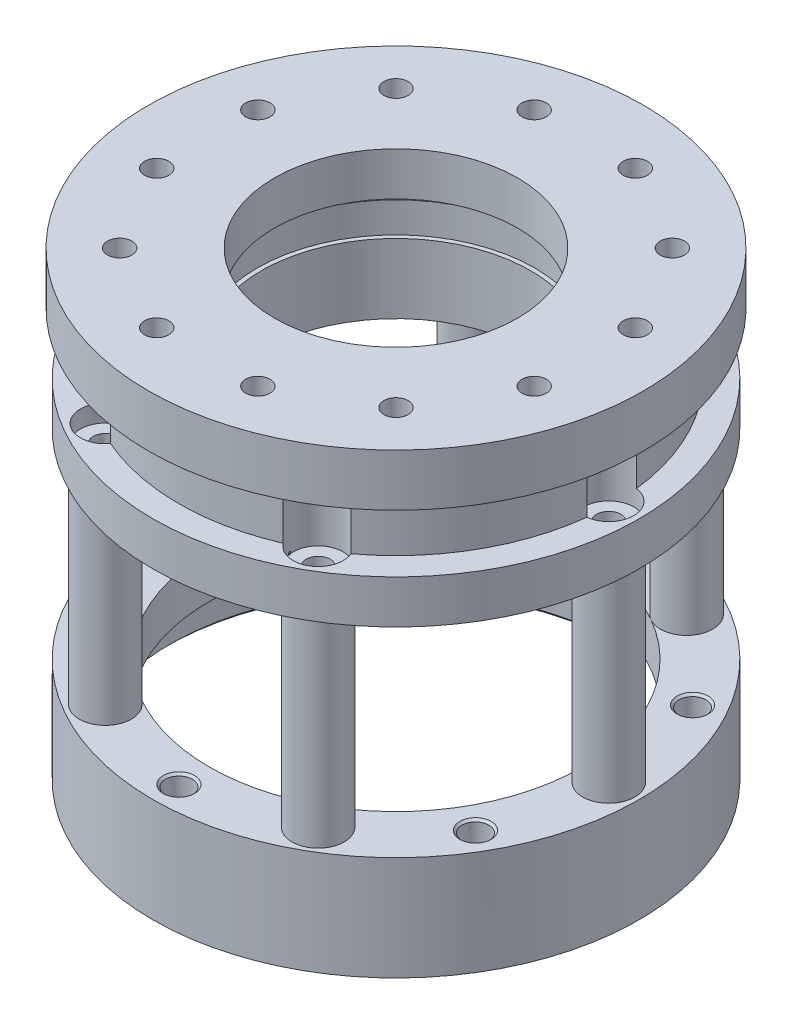
SolidWorks part; units mm, degrees
ref_plane "Front" through (0, 0, 0) normal (0, 0, 1) x (1, 0, 0)
ref_plane "Top" through (0, 0, 0) normal (0, 1, 0) x (1, 0, 0)
ref_plane "Right" through (0, 0, 0) normal (1, 0, 0) x (0, 0, -1)
sketch "Sketch1" plane through (0, 0, 0) normal (0, 1, 0) x (1, 0, 0)
  line L0 (0, 0) -> (24.5, 0) construction
  circle A0 centre (24.5, 0) radius 3
  dimension "D2" = 6
  dimension "D1" = 24.5
extrude "Boss-Extrude1" add sketch "Sketch1" along normal blind 23
ref_axis "Axis1" through (0, -50, 0) along (0, 1, 0)
pattern_circular "CirPattern1" count 6 over 360 about axis through (0, -50, 0) along (0, 1, 0) of "Boss-Extrude1"
sketch "Sketch3" plane through (0, 0, 0) normal (0, 1, 0) x (1, 0, 0)
  circle A0 centre (0, 0) radius 28
  circle A1 centre (0, 0) radius 21.5
  dimension "D1" = 56
  dimension "D2" = 43
extrude "Boss-Extrude2" add sketch "Sketch3" against normal blind 5
sketch "Sketch4" plane through (0, -5, 0) normal (0, -1, 0) x (1, 0, 0)
  circle A0 centre (0, 0) radius 26
  circle A1 centre (0, 0) radius 28 construction
  circle A2 centre (0, 0) radius 28
  dimension "D1" = 52
extrude "Boss-Extrude3" add sketch "Sketch4" along normal blind 7
sketch "Sketch5" plane through (0, 0, 0) normal (0, 1, 0) x (1, 0, 0)
  line L0 (0, 0) -> (21.5, 0) construction
  line L1 (0, 0) -> (21.6506, -12.5) construction
  circle A0 centre (0, 0) radius 21.5 construction
  circle A1 centre (21.6506, -12.5) radius 1.55
  circle A2 centre (0, -25) radius 1.55
  circle A3 centre (-21.6506, -12.5) radius 1.55
  circle A4 centre (-21.6506, 12.5) radius 1.55
  circle A5 centre (0, 25) radius 1.55
  circle A6 centre (21.6506, 12.5) radius 1.55
  dimension "D3" = 3.1
  dimension "D1" = 25
  dimension "D2" = 30
  dimension "D4" = 6
extrude "Cut-Extrude1" cut sketch "Sketch5" against normal blind 4
chamfer "Chamfer1" distance 0.25 angle 45 6 edges at (0, 0, -23.45) (-21.6506, 0, -10.95) (-21.6506, 0, 14.05) (0, 0, 26.55) (21.6506, 0, 14.05) (21.6506, 0, -10.95)
sketch "Sketch6" plane through (0, 23, 0) normal (0, 1, 0) x (1, 0, 0)
  circle A0 centre (0, 0) radius 28
  circle A1 centre (0, 0) radius 15.5
  dimension "D1" = 56
  dimension "D2" = 31
extrude "Boss-Extrude4" add sketch "Sketch6" along normal blind 5 separate body
sketch "Sketch7" plane through (0, 28, 0) normal (0, 1, 0) x (1, 0, 0)
  circle A0 centre (0, 0) radius 25
  circle A1 centre (0, 0) radius 15.5 construction
  circle A2 centre (0, 0) radius 15.5
  dimension "D1" = 50
extrude "Boss-Extrude5" add sketch "Sketch7" along normal blind 7
sketch "Sketch8" plane through (0, 35, 0) normal (0, 1, 0) x (1, 0, 0)
  circle A0 centre (0, 0) radius 16
  dimension "D1" = 32
extrude "Cut-Extrude2" cut sketch "Sketch8" against normal blind 4
sketch "Sketch9" plane through (0, 23, 0) normal (0, -1, 0) x (1, 0, 0)
  circle A0 centre (21.6506, 12.5) radius 1.55 construction
  circle A1 centre (21.6506, 12.5) radius 1.55
extrude "Cut-Extrude3" cut sketch "Sketch9" against normal blind 4.5
chamfer "Chamfer2" distance 0.25 angle 45 1 edges at (21.6506, 23, 10.95)
pattern_circular "CirPattern2" count 6 over 360 about axis through (0, 35, 0) along (0, -1, 0) of "Chamfer2", "Cut-Extrude3"
sketch "Sketch10" plane through (0, 35, 0) normal (0, 1, 0) x (1, 0, 0)
  circle A0 centre (0, 0) radius 28.5
  circle A1 centre (0, 0) radius 14
  dimension "D1" = 57
  dimension "D2" = 28
extrude "Boss-Extrude6" add sketch "Sketch10" along normal blind 6 separate body
sketch "Sketch11" plane through (0, 28, 0) normal (0, 1, 0) x (1, 0, 0)
  circle A0 centre (24.5, 0) radius 2.875
  dimension "D1" = 5.75
extrude "Cut-Extrude4" cut sketch "Sketch11" against normal blind 2 and the other way up to surface (7 mm away) other way up to face at (0, 35, 28.5)
sketch "Sketch12" plane through (0, 26, 0) normal (0, 1, 0) x (1, 0, 0)
  circle A0 centre (24.5, 0) radius 1.4
  dimension "D1" = 2.8
extrude "Cut-Extrude5" cut sketch "Sketch12" against normal blind 28
pattern_circular "CirPattern3" count 6 over 360 about axis through (0, 35, 0) along (0, -1, 0) of "Cut-Extrude4", "Cut-Extrude5" reverse direction yes
chamfer "Chamfer3" distance 0.5 angle 45 1 edges at (0, -12, -26)
sketch "Sketch13" plane through (0, 41, 0) normal (0, 1, 0) x (1, 0, 0)
  line L0 (0, 0) -> (18.4774, 0) construction
  line L1 (0, 0) -> (21.7333, -5.8234) construction
  circle A1 centre (0, 0) radius 16 construction
  circle A2 centre (0, 0) radius 16 construction
  arc A3 (14.8909, -20.0813) -> (24.8364, -2.8552) centre (0, 0) ccw construction
  arc A4 (14.8909, -20.0813) -> (24.8364, -2.8552) centre (0, 0) ccw construction
  circle A5 centre (21.7333, -5.8234) radius 1.4
  circle A6 centre (15.9099, -15.9099) radius 1.4
  circle A7 centre (5.8234, -21.7333) radius 1.4
  circle A8 centre (-5.8234, -21.7333) radius 1.4
  circle A9 centre (-15.9099, -15.9099) radius 1.4
  circle A10 centre (-21.7333, -5.8234) radius 1.4
  circle A11 centre (-21.7333, 5.8234) radius 1.4
  circle A12 centre (-15.9099, 15.9099) radius 1.4
  circle A13 centre (-5.8234, 21.7333) radius 1.4
  circle A14 centre (5.8234, 21.7333) radius 1.4
  circle A15 centre (15.9099, 15.9099) radius 1.4
  circle A16 centre (21.7333, 5.8234) radius 1.4
  dimension "D1" = 2.8
  dimension "D2" = 15
  dimension "D3" = 22.5
  dimension "D4" = 12
extrude "Cut-Extrude6" cut sketch "Sketch13" against normal blind 16
sketch "Sketch14" plane through (0, 23, 0) normal (0, -1, 0) x (1, 0, 0)
  line L0 (0, 0) -> (8.5317, 0) construction
  line L1 (0, 0) -> (21.7333, 5.8234) construction
  line L2 (24.9083, -7.6565) -> (24.9083, -3.9903)
  line L3 (25.3995, 5.8234) -> (23.5664, 8.9984)
  line L4 (23.5664, 8.9984) -> (19.9002, 8.9984)
  line L5 (19.9002, 8.9984) -> (18.0672, 5.8234)
  line L6 (18.0672, 5.8234) -> (19.9002, 2.6484)
  line L7 (19.9002, 2.6484) -> (23.5664, 2.6484)
  line L8 (23.5664, 2.6484) -> (25.3995, 5.8234)
  line L9 (24.9083, -3.9903) -> (21.7333, -2.1573)
  line L10 (21.7333, -2.1573) -> (18.5583, -3.9903)
  line L11 (18.5583, -3.9903) -> (18.5583, -7.6565)
  line L12 (18.5583, -7.6565) -> (21.7333, -9.4896)
  line L13 (21.7333, -9.4896) -> (24.9083, -7.6565)
  line L14 (17.743, -19.0849) -> (19.5761, -15.9099)
  line L15 (19.5761, -15.9099) -> (17.743, -12.7349)
  line L16 (17.743, -12.7349) -> (14.0768, -12.7349)
  line L17 (14.0768, -12.7349) -> (12.2437, -15.9099)
  line L18 (12.2437, -15.9099) -> (14.0768, -19.0849)
  line L19 (14.0768, -19.0849) -> (17.743, -19.0849)
  line L20 (5.8234, -25.3995) -> (8.9984, -23.5664)
  line L21 (8.9984, -23.5664) -> (8.9984, -19.9002)
  line L22 (8.9984, -19.9002) -> (5.8234, -18.0672)
  line L23 (5.8234, -18.0672) -> (2.6484, -19.9002)
  line L24 (2.6484, -19.9002) -> (2.6484, -23.5664)
  line L25 (2.6484, -23.5664) -> (5.8234, -25.3995)
  line L26 (-7.6565, -24.9083) -> (-3.9903, -24.9083)
  line L27 (-3.9903, -24.9083) -> (-2.1573, -21.7333)
  line L28 (-2.1573, -21.7333) -> (-3.9903, -18.5583)
  line L29 (-3.9903, -18.5583) -> (-7.6565, -18.5583)
  line L30 (-7.6565, -18.5583) -> (-9.4896, -21.7333)
  line L31 (-9.4896, -21.7333) -> (-7.6565, -24.9083)
  line L32 (-19.0849, -17.743) -> (-15.9099, -19.5761)
  line L33 (-15.9099, -19.5761) -> (-12.7349, -17.743)
  line L34 (-12.7349, -17.743) -> (-12.7349, -14.0768)
  line L35 (-12.7349, -14.0768) -> (-15.9099, -12.2437)
  line L36 (-15.9099, -12.2437) -> (-19.0849, -14.0768)
  line L37 (-19.0849, -14.0768) -> (-19.0849, -17.743)
  line L38 (-25.3995, -5.8234) -> (-23.5664, -8.9984)
  line L39 (-23.5664, -8.9984) -> (-19.9002, -8.9984)
  line L40 (-19.9002, -8.9984) -> (-18.0672, -5.8234)
  line L41 (-18.0672, -5.8234) -> (-19.9002, -2.6484)
  line L42 (-19.9002, -2.6484) -> (-23.5664, -2.6484)
  line L43 (-23.5664, -2.6484) -> (-25.3995, -5.8234)
  line L44 (-24.9083, 7.6565) -> (-24.9083, 3.9903)
  line L45 (-24.9083, 3.9903) -> (-21.7333, 2.1573)
  line L46 (-21.7333, 2.1573) -> (-18.5583, 3.9903)
  line L47 (-18.5583, 3.9903) -> (-18.5583, 7.6565)
  line L48 (-18.5583, 7.6565) -> (-21.7333, 9.4896)
  line L49 (-21.7333, 9.4896) -> (-24.9083, 7.6565)
  line L50 (-17.743, 19.0849) -> (-19.5761, 15.9099)
  line L51 (-19.5761, 15.9099) -> (-17.743, 12.7349)
  line L52 (-17.743, 12.7349) -> (-14.0768, 12.7349)
  line L53 (-14.0768, 12.7349) -> (-12.2437, 15.9099)
  line L54 (-12.2437, 15.9099) -> (-14.0768, 19.0849)
  line L55 (-14.0768, 19.0849) -> (-17.743, 19.0849)
  line L56 (-5.8234, 25.3995) -> (-8.9984, 23.5664)
  line L57 (-8.9984, 23.5664) -> (-8.9984, 19.9002)
  line L58 (-8.9984, 19.9002) -> (-5.8234, 18.0672)
  line L59 (-5.8234, 18.0672) -> (-2.6484, 19.9002)
  line L60 (-2.6484, 19.9002) -> (-2.6484, 23.5664)
  line L61 (-2.6484, 23.5664) -> (-5.8234, 25.3995)
  line L62 (7.6565, 24.9083) -> (3.9903, 24.9083)
  line L63 (3.9903, 24.9083) -> (2.1573, 21.7333)
  line L64 (2.1573, 21.7333) -> (3.9903, 18.5583)
  line L65 (3.9903, 18.5583) -> (7.6565, 18.5583)
  line L66 (7.6565, 18.5583) -> (9.4896, 21.7333)
  line L67 (9.4896, 21.7333) -> (7.6565, 24.9083)
  line L68 (19.0849, 17.743) -> (15.9099, 19.5761)
  line L69 (15.9099, 19.5761) -> (12.7349, 17.743)
  line L70 (12.7349, 17.743) -> (12.7349, 14.0768)
  line L71 (12.7349, 14.0768) -> (15.9099, 12.2437)
  line L72 (15.9099, 12.2437) -> (19.0849, 14.0768)
  line L73 (19.0849, 14.0768) -> (19.0849, 17.743)
  circle A0 centre (21.7333, 5.8234) radius 3.175 construction
  circle A1 centre (21.7333, -5.8234) radius 3.175 construction
  circle A2 centre (15.9099, -15.9099) radius 3.175 construction
  circle A3 centre (5.8234, -21.7333) radius 3.175 construction
  circle A4 centre (-5.8234, -21.7333) radius 3.175 construction
  circle A5 centre (-15.9099, -15.9099) radius 3.175 construction
  circle A6 centre (-21.7333, -5.8234) radius 3.175 construction
  circle A7 centre (-21.7333, 5.8234) radius 3.175 construction
  circle A8 centre (-15.9099, 15.9099) radius 3.175 construction
  circle A9 centre (-5.8234, 21.7333) radius 3.175 construction
  circle A10 centre (5.8234, 21.7333) radius 3.175 construction
  circle A11 centre (15.9099, 15.9099) radius 3.175 construction
  dimension "D1" = 15
  dimension "D2" = 22.5
  dimension "D3" = 6.35
  dimension "D4" = 12
extrude "Cut-Extrude7" cut sketch "Sketch14" against normal blind 3.25
chamfer "Chamfer4" distance 0.5 angle 45 7 edges at (0, 35, 16) (0, 35, 25) (21.6506, 35, 12.5) (21.6506, 35, -12.5) (0, 35, -25) (-21.6506, 35, -12.5) (-21.6506, 35, 12.5)
sketch "Sketch15" plane through (0, 41, 0) normal (0, 1, 0) x (1, 0, 0)
  line L0 (0, 0) -> (200, 0) construction
  line L1 (2.3571, 28.4024) -> (200, 12)
  line L2 (200, -12) -> (2.3571, -28.4024)
  circle A0 centre (0, 0) radius 17.3405
  arc A1 (2.3571, 28.4024) -> (2.3571, -28.4024) centre (0, 0) ccw
  arc A2 (200, -12) -> (200, 12) centre (200, 0) ccw
  circle A3 centre (0, 0) radius 28.5 construction
  dimension "D1" = 200
  dimension "D2" = 24
extrude "Boss-Extrude7" add sketch "Sketch15" along normal blind 6 separate body
sketch "Sketch16" plane through (0, 47, 0) normal (0, 1, 0) x (1, 0, 0)
  circle A0 centre (200, 0) radius 6
  dimension "D1" = 12
extrude "Boss-Extrude8" add sketch "Sketch16" along normal blind 14
sketch "Sketch17" plane through (0, 61, 0) normal (0, 1, 0) x (1, 0, 0)
  circle A0 centre (200, 0) radius 10
  dimension "D1" = 20
extrude "Boss-Extrude9" add sketch "Sketch17" along normal blind 4
sketch "Sketch18" plane through (0, 47, 0) normal (0, 1, 0) x (1, 0, 0)
  circle A0 centre (52.1814, 0) radius 14.0548
  circle A1 centre (88.1102, 0) radius 8.9972
  circle A2 centre (119.7664, 0) radius 7.2286
  circle A3 centre (149.4804, 0) radius 5.4975
extrude "Cut-Extrude8" cut sketch "Sketch18" against normal through all
sketch "Sketch20" plane through (0, 47, 0) normal (0, 1, 0) x (1, 0, 0)
  circle A0 centre (21.7333, 5.8234) radius 1.4 construction
  circle A1 centre (21.7333, -5.8234) radius 1.4 construction
  circle A2 centre (21.7333, 5.8234) radius 1.4
  circle A3 centre (21.7333, -5.8234) radius 1.4
  circle A4 centre (15.9099, -15.9099) radius 1.4 construction
  circle A5 centre (5.8234, -21.7333) radius 1.4 construction
  circle A6 centre (-5.8234, -21.7333) radius 1.4 construction
  circle A7 centre (-15.9099, -15.9099) radius 1.4 construction
  circle A8 centre (-21.7333, -5.8234) radius 1.4 construction
  circle A9 centre (-21.7333, 5.8234) radius 1.4 construction
  circle A10 centre (-15.9099, 15.9099) radius 1.4 construction
  circle A11 centre (-5.8234, 21.7333) radius 1.4 construction
  circle A12 centre (5.8234, 21.7333) radius 1.4 construction
  circle A13 centre (15.9099, 15.9099) radius 1.4 construction
  circle A14 centre (15.9099, -15.9099) radius 1.4
  circle A15 centre (5.8234, -21.7333) radius 1.4
  circle A16 centre (-5.8234, -21.7333) radius 1.4
  circle A17 centre (-15.9099, -15.9099) radius 1.4
  circle A18 centre (-21.7333, -5.8234) radius 1.4
  circle A19 centre (-21.7333, 5.8234) radius 1.4
  circle A20 centre (-15.9099, 15.9099) radius 1.4
  circle A21 centre (-5.8234, 21.7333) radius 1.4
  circle A22 centre (5.8234, 21.7333) radius 1.4
  circle A23 centre (15.9099, 15.9099) radius 1.4
extrude "Cut-Extrude9" cut sketch "Sketch20" against normal up to surface (6 mm away) up to face at (52.1814, 41, 14.0548)
sketch "Sketch21" plane through (0, 35, 0) normal (0, -1, 0) x (1, 0, 0)
  circle A0 centre (0, 0) radius 16
  dimension "D1" = 32
extrude "Cut-Extrude10" cut sketch "Sketch21" against normal blind 1
sketch "Sketch22" [suppressed] plane through (0, -4, 0) normal (0, 1, 0) x (1, 0, 0)
  circle A1 centre (21.6506, -12.5) radius 1.55
  circle A2 centre (21.6506, -12.5) radius 1.55
  dimension "D1" = 0
extrude "Boss-Extrude10" [suppressed] add sketch "Sketch22" along normal up to surface (31.5 mm away) separate body up to face at (21.6506, 27.5, 10.95)
pattern_circular "CirPattern5" [suppressed] count 6 over 360 reverse direction yes of bodies 133
sketch "Sketch23" [suppressed] plane through (0, 23, 0) normal (0, 1, 0) x (1, 0, 0)
  circle A0 centre (12.25, -21.2176) radius 1.4 construction
  circle A1 centre (12.25, -21.2176) radius 3
  circle A2 centre (12.25, -21.2176) radius 3
  circle A3 centre (12.25, -21.2176) radius 1.4
  dimension "D1" = 0
extrude "Boss-Extrude11" [suppressed] add sketch "Sketch23" along normal blind 2 separate body
sketch "Sketch24" [suppressed] plane through (0, 41, 0) normal (0, 1, 0) x (1, 0, 0)
  line L0 (0, 0) -> (200, 0) construction
  line L1 (3.0625, 34.8658) -> (201.5313, 17.4329)
  line L2 (3.0625, -34.8658) -> (201.5313, -17.4329)
  circle A4 centre (0, 0) radius 14 construction
  circle A5 centre (0, 0) radius 14
  arc A6 (3.0625, 34.8658) -> (3.0625, -34.8658) centre (0, 0) ccw
  arc A7 (201.5313, -17.4329) -> (201.5313, 17.4329) centre (200, 0) ccw
  arc A8 (35, 0) -> (3.0625, 34.8658) centre (0, 0) ccw construction
  arc A9 (3.0625, -34.8658) -> (35, 0) centre (0, 0) ccw construction
  arc A10 (182.5, 0) -> (201.5313, -17.4329) centre (200, 0) ccw construction
  arc A11 (201.5313, 17.4329) -> (182.5, 0) centre (200, 0) ccw construction
  dimension "D2" = 70
  dimension "D3" = 35
  dimension "D1" = 200
extrude "Boss-Extrude12" [suppressed] add sketch "Sketch24" along normal blind 20 separate body
sketch "Sketch25" [suppressed] plane through (0, 61, 0) normal (0, 1, 0) x (1, 0, 0)
  line L0 (0, 0) -> (200, 0) construction
  line L1 (200, 0) -> (210, 0) construction
  circle A0 centre (59.8852, 0) radius 20.3471
  circle A1 centre (116.238, 0) radius 16.1539
  circle A2 centre (164.0017, 0) radius 10.0532
  circle A3 centre (210, 0) radius 1.4
  circle A4 centre (203.0902, -9.5106) radius 1.4
  circle A5 centre (191.9098, -5.8779) radius 1.4
  circle A6 centre (191.9098, 5.8779) radius 1.4
  circle A7 centre (203.0902, 9.5106) radius 1.4
  dimension "D3" = 2.8
  dimension "D1" = 200
  dimension "D2" = 10
  dimension "D4" = 5
extrude "Cut-Extrude11" [suppressed] cut sketch "Sketch25" against normal up to surface (20 mm away) up to face at (21.7333, 41, 7.2234)
sketch "Sketch27" [suppressed] plane through (0, 61, 0) normal (0, 1, 0) x (1, 0, 0)
  circle A3 centre (21.7333, 5.8234) radius 1.4
  circle A4 centre (21.7333, 5.8234) radius 1.4
  circle A5 centre (15.9099, 15.9099) radius 1.4
  circle A6 centre (15.9099, 15.9099) radius 1.4
  circle A7 centre (5.8234, 21.7333) radius 1.4
  circle A8 centre (5.8234, 21.7333) radius 1.4
  circle A9 centre (-5.8234, 21.7333) radius 1.4
  circle A10 centre (-5.8234, 21.7333) radius 1.4
  circle A11 centre (-15.9099, 15.9099) radius 1.4
  circle A12 centre (-15.9099, 15.9099) radius 1.4
  circle A13 centre (-21.7333, 5.8234) radius 1.4
  circle A14 centre (-21.7333, 5.8234) radius 1.4
  circle A15 centre (-21.7333, -5.8234) radius 1.4
  circle A16 centre (-21.7333, -5.8234) radius 1.4
  circle A17 centre (-15.9099, -15.9099) radius 1.4
  circle A18 centre (-15.9099, -15.9099) radius 1.4
  circle A19 centre (-5.8234, -21.7333) radius 1.4
  circle A20 centre (-5.8234, -21.7333) radius 1.4
  circle A21 centre (5.8234, -21.7333) radius 1.4
  circle A22 centre (5.8234, -21.7333) radius 1.4
  circle A23 centre (15.9099, -15.9099) radius 1.4
  circle A24 centre (15.9099, -15.9099) radius 1.4
  circle A25 centre (21.7333, -5.8234) radius 1.4
  circle A26 centre (21.7333, -5.8234) radius 1.4
  dimension "D2" = 0
  dimension "D3" = 0
  dimension "D4" = 0
  dimension "D5" = 0
  dimension "D6" = 0
  dimension "D7" = 0
  dimension "D8" = 0
  dimension "D9" = 0
  dimension "D10" = 0
  dimension "D11" = 0
  dimension "D12" = 0
  dimension "D13" = 0
extrude "Cut-Extrude12" [suppressed] cut sketch "Sketch27" against normal up to surface (20 mm away) up to face at (21.7333, 41, 7.2234)
fillet "Fillet1" [suppressed] radius 5
delete or keep bodies "Body-Delete/Keep 1" bodies 131
